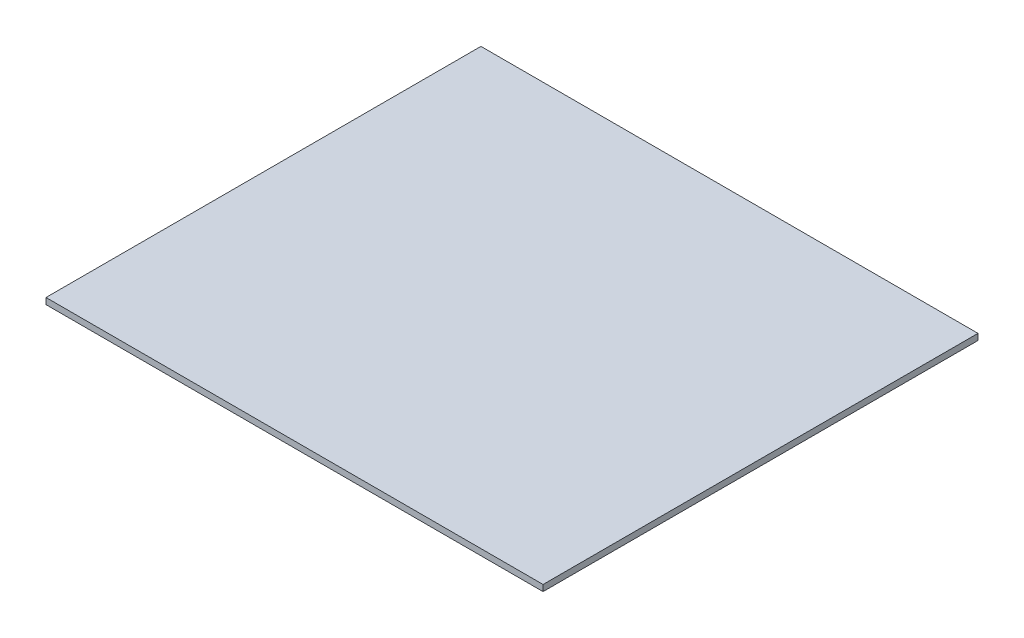
SolidWorks part; units mm, degrees
ref_plane "Front Plane" through (0, 0, 0) normal (0, 0, 1) x (1, 0, 0)
ref_plane "Top Plane" through (0, 0, 0) normal (0, 1, 0) x (1, 0, 0)
ref_plane "Right Plane" through (0, 0, 0) normal (1, 0, 0) x (0, 0, -1)
sketch "Sketch2" plane through (0, 0, 0) normal (0, 1, 0) x (1, 0, 0)
  line L1 (0, 0) -> (400, 0)
  line L2 (0, 0) -> (0, 350)
  line L3 (0, 350) -> (400, 350)
  line L4 (400, 0) -> (400, 350)
  dimension "D1" = 400
  dimension "D2" = 350
extrude "Boss-Extrude1" add sketch "Sketch2" along normal blind 5
